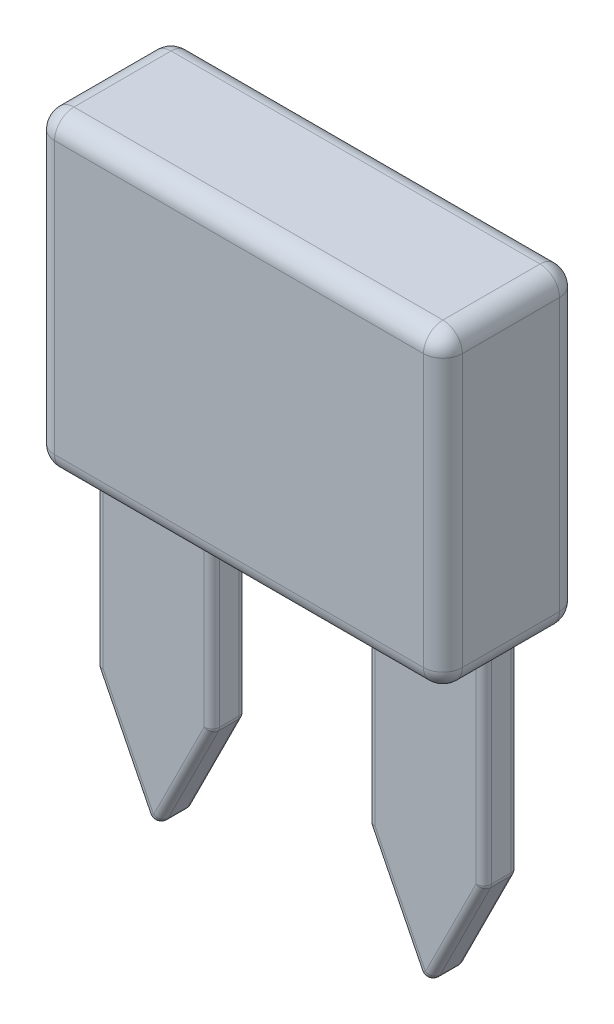
SolidWorks part; units mm, degrees
material "AISI 1020"
ref_plane "Front Plane" through (0, 0, 0) normal (0, 0, 1) x (1, 0, 0)
ref_plane "Top Plane" through (0, 0, 0) normal (0, 1, 0) x (1, 0, 0)
ref_plane "Right Plane" through (0, 0, 0) normal (1, 0, 0) x (0, 0, -1)
sketch "Sketch1" plane through (0, 0, 0) normal (0, 0, 1) x (1, 0, 0)
  line L0 (5, 5) -> (2, 5)
  line L1 (2, 5) -> (2, 0)
  line L2 (2, 0) -> (3.5, -3)
  line L3 (3.5, -3) -> (5, 0)
  line L4 (5, 0) -> (5, 5)
  line L5 (-2, 5) -> (-5, 5)
  line L6 (-5, 5) -> (-5, 0)
  line L7 (-5, 0) -> (-3.5, -3)
  line L8 (-3.5, -3) -> (-2, 0)
  line L9 (-2, 0) -> (-2, 5)
  line L10 (2, 0) -> (-2, 0) construction
  point P7 (2.1783, 0)
  point P11 (-3.1137, -2.0313)
  point P12 (-3.5, -2.1738)
  point P13 (3.5, 5)
  point P15 (-3.5, 5)
  point P20 (0, 0)
  dimension "D1" = 4
  dimension "D2" = 10
  dimension "D3" = 5
  dimension "D4" = 3
extrude "Boss-Extrude1" add sketch "Sketch1" along normal mid plane 0.9
sketch "Sketch3" plane through (0, 0, 0) normal (1, 0, 0) x (0, 0, -1)
  line L0 (-0.45, 5) -> (0.45, 5) construction
  line L1 (-1.75, 13) -> (1.75, 13)
  line L2 (-1.75, 13) -> (-1.75, 5)
  line L3 (-1.75, 5) -> (1.75, 5)
  line L4 (1.75, 13) -> (1.75, 5)
  line L5 (-1.75, 13) -> (1.75, 5) construction
  line L6 (-1.75, 5) -> (1.75, 13) construction
  line L7 (-0.45, -3) -> (0.45, -3) construction
  point P0 (0, 9)
  point P5 (0, 5)
  point P8 (0, 5)
  dimension "D1" = 16
  dimension "D2" = 3.5
extrude "Boss-Extrude2" add sketch "Sketch3" along normal mid plane 10.5
fillet "Fillet1" radius 0.2 22 edges at (-5, 0, 0) (-4.25, -1.5, 0.45) (-4.25, -1.5, -0.45) (-3.5, -3, 0) (-2.75, -1.5, 0.45) (-2, 0, 0) (-2.75, -1.5, -0.45) (-2, 2.5, 0.45) (-5, 2.5, 0.45) (-5, 2.5, -0.45) (-2, 2.5, -0.45) (2.75, -1.5, 0.45) (2, 2.5, 0.45) (2, 0, 0) (2, 2.5, -0.45) (3.5, -3, 0) (2.75, -1.5, -0.45) (5, 0, 0) (4.25, -1.5, 0.45) (4.25, -1.5, -0.45) (5, 2.5, 0.45) (5, 2.5, -0.45)
fillet "Fillet2" radius 0.5 12 edges at (5.25, 5, 0) (5.25, 13, 0) (-5.25, 13, 0) (-5.25, 5, 0) (0, 13, 1.75) (5.25, 9, 1.75) (0, 5, 1.75) (-5.25, 9, 1.75) (0, 5, -1.75) (5.25, 9, -1.75) (0, 13, -1.75) (-5.25, 9, -1.75)
